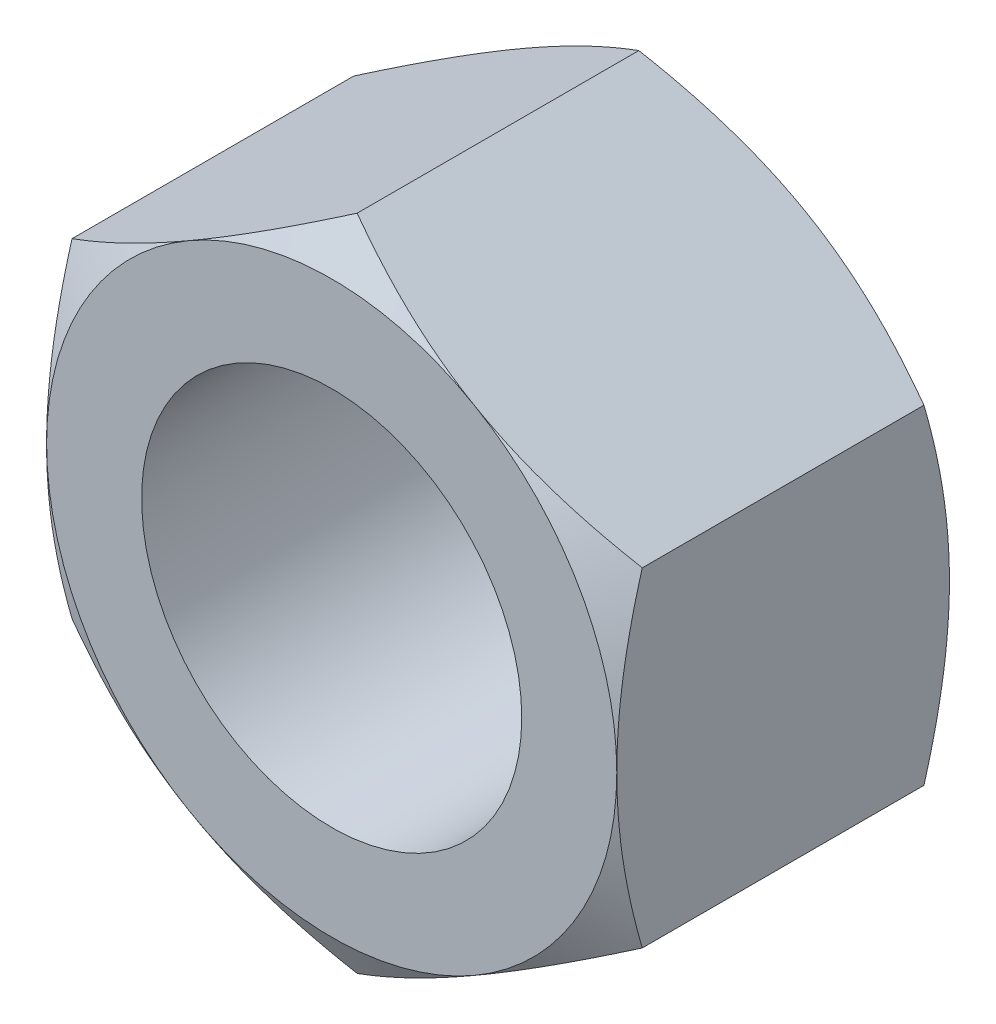
SolidWorks part; units mm, degrees
ref_plane "Front" through (0, 0, 0) normal (0, 0, 1) x (1, 0, 0)
ref_plane "Top" through (0, 0, 0) normal (0, 1, 0) x (1, 0, 0)
ref_plane "Right" through (0, 0, 0) normal (1, 0, 0) x (0, 0, -1)
sketch "Sketch1" plane through (0, 0, 0) normal (0, 0, 1) x (1, 0, 0)
  line L1 (-9.525, 5.4993) -> (-9.525, -5.4993)
  line L2 (-9.525, -5.4993) -> (0, -10.9985)
  line L3 (0, -10.9985) -> (9.525, -5.4993)
  line L4 (9.525, -5.4993) -> (9.525, 5.4993)
  line L5 (9.525, 5.4993) -> (0, 10.9985)
  line L6 (0, 10.9985) -> (-9.525, 5.4993)
  circle A0 centre (0, 0) radius 9.525 construction
  circle A1 centre (0, 0) radius 6.35
  point P10 (0, 6.35)
  dimension "hex" = 19.05
  dimension "dia" = 12.7
extrude "Extrude1" add sketch "Sketch1" along normal mid plane 11.1125
sketch "Sketch4" plane through (0, 0, -5.5562) normal (0, 0, -1) x (-1, 0, 0)
  circle A0 centre (0, 0) radius 6.35 construction
  circle A1 centre (0, 0) radius 6.35
curve "Helix/Spiral3" pitch 1.9538 height 13.335 turns 6.825
sketch "Sketch3" plane through (0, 0, 0) normal (1, 0, 0) x (0, 0, -1)
  line L0 (5.5562, 6.35) -> (7.2659, 6.35)
  line L1 (7.2659, 6.35) -> (6.5332, 5.0809)
  line L2 (6.5332, 5.0809) -> (6.2889, 5.0809)
  line L3 (6.2889, 5.0809) -> (5.5562, 6.35)
  line L4 (5.9226, 5.7155) -> (6.8995, 5.7155) construction
  dimension "D1" = 60
  dimension "D2" = 0.9769
  dimension "D3" = 0.2442
sweep "Sweep1" [suppressed] add profiles "Sketch3" path "Helix/Spiral3"
sketch "Sketch6" [suppressed] plane through (0, 0, 0) normal (1, 0, 0) x (0, 0, -1)
  line L0 (-6.0447, 6.8385) -> (-5.0678, 5.8615)
  line L1 (-5.0678, 5.8615) -> (-5.0678, 0) construction
  line L2 (7.7378, 0) -> (-7.7378, 0) construction
  line L3 (-5.0678, 0) -> (-7.7781, 0)
  line L4 (-7.7781, 0) -> (-7.7781, 6.8385)
  line L5 (-7.7781, 6.8385) -> (-6.0447, 6.8385)
  line L6 (-5.0678, 5.8615) -> (0.7937, 0)
  line L7 (0.7937, 0) -> (-5.0678, 0)
  line L8 (-5.5562, -5.4993) -> (-5.5562, 5.4993) construction
  point P2 (-5.5562, 6.35)
  dimension "D2" = 0.9769
  dimension "D1" = 45
revolve "Cut-Revolve1" [suppressed] cut sketch "Sketch6" angle 360 about L3
sketch "Sketch7" plane through (0, 0, 5.5562) normal (0, 0, 1) x (1, 0, 0)
  circle A0 centre (0, 0) radius 9.525 construction
  circle A1 centre (0, 0) radius 9.525
extrude "Extrude2" cut sketch "Sketch7" against normal blind 25.4 draft 60 flip side to cut
mirror "Mirror1" about plane through (0, 0, 0) normal (0, 0, 1) of "Extrude2", "Cut-Revolve1"
sketch "Sketch8" [suppressed] plane through (0, 0, 5.5562) normal (0, 0, 1) x (1, 0, 0)
  line L0 (-4.4901, 4.4901) -> (0, 0) construction
  line L1 (0, -7.7378) -> (0, 7.7378) construction
  circle A0 centre (0, 0) radius 6.35 construction
  point P0 (-4.4901, 4.4901)
  dimension "D1" = 45
equation "\"D3@Helix/Spiral3\" = \"length@Extrude1\" * 1.2"
equation "\"D2@Sketch3\" = \"D4@Helix/Spiral3\" * .5"
equation "\"D3@Sketch3\" = \"D4@Helix/Spiral3\" * .125"
equation "\"D2@Sketch6\" = \"D4@Helix/Spiral3\" * .5"
